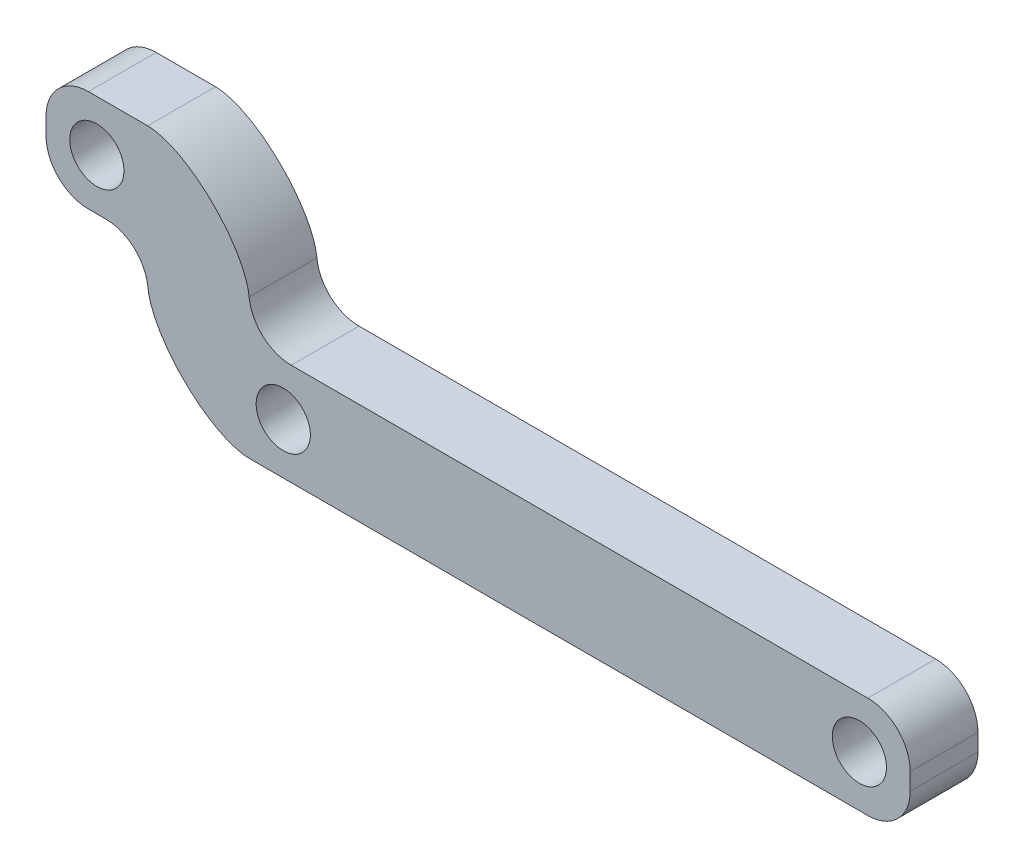
SolidWorks part; units mm, degrees
ref_plane "Front" through (0, 0, 0) normal (0, 0, 1) x (1, 0, 0)
ref_plane "Top" through (0, 0, 0) normal (0, 1, 0) x (1, 0, 0)
ref_plane "Right" through (0, 0, 0) normal (1, 0, 0) x (0, 0, -1)
sketch "Sketch1" plane through (0, 0, 0) normal (0, 0, 1) x (1, 0, 0)
  line L1 (0, 0) -> (-45, 0)
  line L2 (0, 0) -> (0, -6)
  line L3 (0, -6) -> (-45, -6)
  line L4 (-45, 0) -> (-45, -6)
  line L5 (-45, 0) -> (-39, 0)
  line L6 (-45, 0) -> (-45, 8)
  line L7 (-45, 8) -> (-39, 8)
  line L8 (-39, 0) -> (-39, 8)
  line L9 (-45, 8) -> (-51, 8)
  line L10 (-45, 8) -> (-45, 2)
  line L11 (-45, 2) -> (-51, 2)
  line L12 (-51, 8) -> (-51, 2)
  dimension "D1" = 6
  dimension "D2" = 45
  dimension "D3" = 6
  dimension "D4" = 8
  dimension "D5" = 6
  dimension "D6" = 6
extrude "Boss-Extrude1" add sketch "Sketch1" along normal blind 4 contours L1 L4 L3 L2 | L1 L8 L7 L6 | L9 L12 L11 L6 region at (-22.5, -3, 0) region at (-42, 4, 0) region at (-48, 5, 0)
sketch "Sketch2" plane through (0, 0, 0) normal (0, 0, -1) x (-1, 0, 0)
  line L0 (51, 8) -> (39, 8) construction
  line L1 (0, 0) -> (0, -6) construction
  line L2 (51, 8) -> (51, 2) construction
  circle A0 centre (3, -3) radius 1.6
  circle A1 centre (37, -3) radius 1.6
  circle A2 centre (48, 5) radius 1.6
  dimension "D1" = 3.2
  dimension "D2" = 3.2
  dimension "D3" = 3.2
  dimension "D4" = 3
  dimension "D5" = 3
  dimension "D6" = 34
  dimension "D7" = 3
extrude "Cut-Extrude1" cut sketch "Sketch2" against normal through all
fillet "Fillet2" radius 6 2 edges at (-45, -6, 2) (-39, 8, 2) conic rho 0.3
fillet "Fillet3" radius 2.5 6 edges at (-51, 8, 2) (-51, 2, 2) (-45, 2, 2) (-39, 0, 2) (0, 0, 2) (0, -6, 2)
